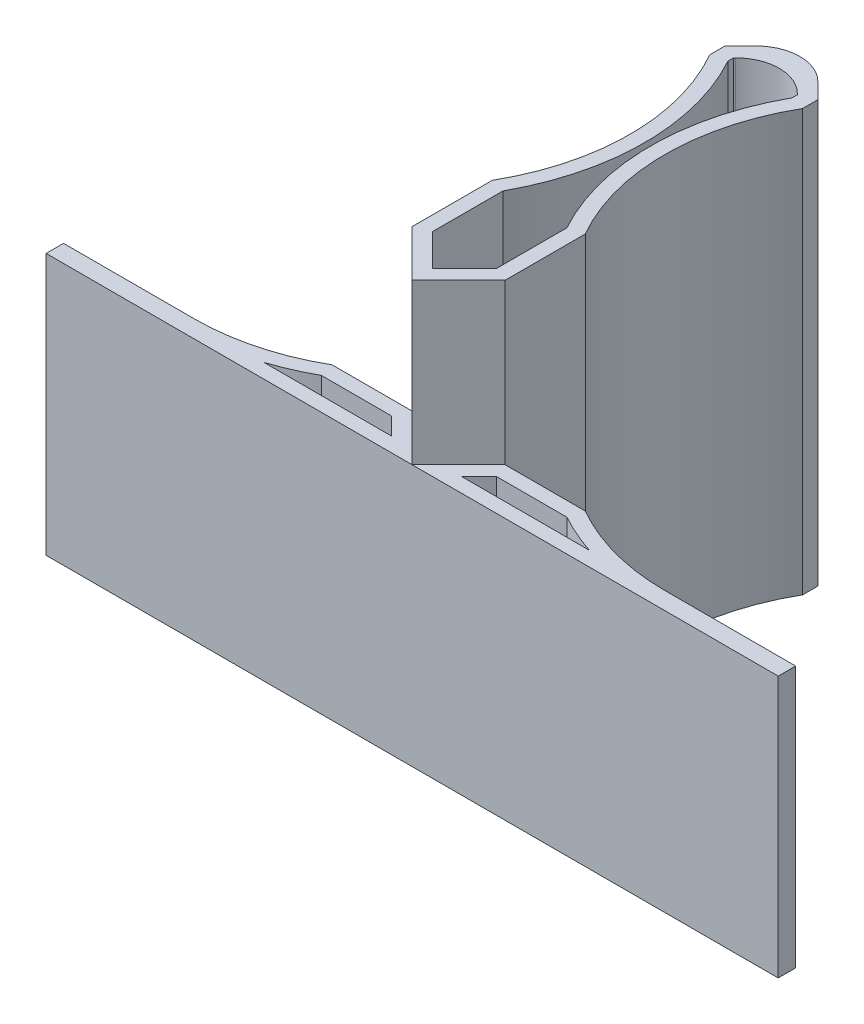
SolidWorks part; units mm, degrees
ref_plane "Front Plane" through (0, 0, 0) normal (0, 0, 1) x (1, 0, 0)
ref_plane "Top Plane" through (0, 0, 0) normal (0, 1, 0) x (1, 0, 0)
ref_plane "Right Plane" through (0, 0, 0) normal (1, 0, 0) x (0, 0, -1)
sketch "Sketch1" plane through (0, 0, 0) normal (0, 1, 0) x (1, 0, 0)
  line L0 (23.7595, 41.275) -> (41.275, 41.275) construction
  line L1 (-41.275, -41.275) -> (-23.7595, -41.275) construction
  line L2 (-41.275, -41.275) -> (-41.275, -23.7595) construction
  line L3 (-41.275, 41.275) -> (-23.7595, 41.275) construction
  line L4 (41.275, -41.275) -> (41.275, -23.7595) construction
  line L5 (-41.275, -41.275) -> (41.275, 41.275) construction
  line L6 (-41.275, 41.275) -> (41.275, -41.275) construction
  line L7 (41.275, 23.7595) -> (41.275, 41.275) construction
  line L8 (-41.275, 23.7595) -> (-41.275, 41.275) construction
  line L9 (23.7595, -41.275) -> (41.275, -41.275) construction
  line L10 (24.7569, 45.085) -> (45.085, 45.085) construction
  line L11 (45.085, 24.7569) -> (45.085, 45.085) construction
  line L12 (45.085, -45.085) -> (45.085, -24.7569) construction
  line L13 (24.7569, -45.085) -> (45.085, -45.085) construction
  line L14 (-45.085, -45.085) -> (-24.7569, -45.085) construction
  line L15 (-45.085, -45.085) -> (-45.085, -24.7569) construction
  line L16 (-45.085, 24.7569) -> (-45.085, 45.085) construction
  line L17 (-45.085, 45.085) -> (-24.7569, 45.085) construction
  line L19 (-51.435, -51.435) -> (51.435, -51.435) construction
  line L20 (-51.435, -51.435) -> (-51.435, 51.435) construction
  line L21 (-51.435, 51.435) -> (51.435, 51.435) construction
  line L22 (51.435, -51.435) -> (51.435, 51.435) construction
  line L23 (-51.435, -51.435) -> (51.435, 51.435) construction
  line L24 (-51.435, 51.435) -> (51.435, -51.435) construction
  arc A1 (-41.275, 23.7595) -> (-41.275, -23.7595) centre (0, 0) ccw construction
  arc A2 (23.7595, 41.275) -> (-23.7595, 41.275) centre (0, 0) ccw construction
  arc A3 (-23.7595, -41.275) -> (23.7595, -41.275) centre (0, 0) ccw construction
  arc A4 (41.275, -23.7595) -> (41.275, 23.7595) centre (0, 0) ccw construction
  arc A5 (45.085, -24.7569) -> (45.085, 24.7569) centre (0, 0) ccw construction
  arc A6 (-24.7569, -45.085) -> (24.7569, -45.085) centre (0, 0) ccw construction
  arc A7 (-45.085, 24.7569) -> (-45.085, -24.7569) centre (0, 0) ccw construction
  arc A8 (24.7569, 45.085) -> (-24.7569, 45.085) centre (0, 0) ccw construction
  point P0 (0, 0)
  dimension "D1" = 82.55
  dimension "D2" = 82.55
  dimension "D3" = 95.25
  dimension "D4" = 3.81
sketch "Sketch2" plane through (0, 0, 0) normal (0, 0, 1) x (1, 0, 0)
  line L0 (0, 48) -> (0, 0) construction
  line L1 (0, 0) -> (0, -9.15) construction
  line L2 (0, 48) -> (0, 82.925) construction
  dimension "Cage height" = 48
  dimension "Plate height" = 34.925
  dimension "D1" = 57.15
  dimension "D2" = 9.15
sketch "Sketch13" plane through (0, 0, 0) normal (0, 1, 0) x (1, 0, 0)
  line L0 (-51.435, -51.435) -> (51.435, -51.435) construction
  line L1 (-41.275, -41.275) -> (-23.7595, -41.275) construction
  line L2 (-41.275, -41.275) -> (-41.275, -23.7595) construction
  line L4 (-51.435, -51.435) -> (0, -51.435)
  line L5 (-41.275, -41.275) -> (-23.7595, -41.275)
  line L6 (-41.275, -41.275) -> (-41.275, -23.7595)
  line L9 (0, -47.625) -> (0, -51.435)
  line L10 (-51.435, 51.435) -> (51.435, -51.435) construction
  line L11 (-41.275, 23.7595) -> (-41.275, 41.275) construction
  line L12 (-51.435, -51.435) -> (-51.435, 51.435) construction
  line L13 (-51.435, 51.435) -> (-41.275, 41.275)
  line L14 (-41.275, 23.7595) -> (-41.275, 41.275)
  line L15 (-51.435, -51.435) -> (-51.435, 51.435)
  arc A0 (-23.7595, -41.275) -> (23.7595, -41.275) centre (0, 0) ccw construction
  arc A2 (-23.7595, -41.275) -> (0, -47.625) centre (0, 0) ccw
  arc A4 (-41.275, 23.7595) -> (-41.275, -23.7595) centre (0, 0) ccw construction
  arc A5 (-41.275, 23.7595) -> (-41.275, -23.7595) centre (0, 0) ccw
extrude "Boss-Extrude2" add sketch "Sketch13" along normal up to vertex (82.925 mm away) and the other way up to vertex (9.15 mm away) up to point (0, 82.925, 0) other way up to point (0, -9.15, 0)
sketch "Sketch15" plane through (0, 82.925, 0) normal (0, 1, 0) x (1, 0, 0)
  line L0 (0, 0) -> (-51.435, -51.435)
  line L1 (-51.435, -51.435) -> (0, -51.435)
  line L2 (0, -51.435) -> (0, 0)
  line L3 (-51.435, -51.435) -> (51.435, -51.435) construction
extrude "Cut-Extrude2" cut sketch "Sketch15" against normal up to vertex (34.925 mm away) up to point (0, 48, 0)
mirror "Mirror1" about plane through (-51.435, 82.925, 51.435) normal (1, 0, 0) of "Boss-Extrude2", "Cut-Extrude2"
sketch "Sketch16" plane through (0, -9.15, 0) normal (0, -1, 0) x (1, 0, 0)
  line L1 (-51.435, -51.435) -> (51.435, -51.435) construction
  circle A5 centre (-51.435, -13.335) radius 1.35
  dimension "D1" = 2.7
  dimension "D2" = 38.1
extrude "Cut-Extrude3" cut sketch "Sketch16" against normal blind 31.75
sketch "Sketch17" plane through (0, 82.925, 0) normal (0, 1, 0) x (1, 0, 0)
  line L0 (7.0944, 7.0944) -> (-7.0944, -7.0944)
  line L1 (7.0944, 7.0944) -> (-44.3406, 58.5294)
  line L2 (-7.0944, -7.0944) -> (-51.435, 37.2462)
  line L3 (-44.3406, 58.5294) -> (-51.435, 51.435)
  line L4 (-41.275, -41.275) -> (41.275, 41.275) construction
  line L5 (-61.595, 41.275) -> (-51.435, 51.435) construction
  line L6 (-51.435, -51.435) -> (-51.435, 51.435) construction
  line L7 (-51.435, 7.7321) -> (-51.435, 82.5591) construction
  line L8 (-95.7756, -7.0944) -> (-51.435, 37.2462)
  line L9 (-58.5294, 58.5294) -> (-51.435, 51.435)
  line L10 (-109.9644, 7.0944) -> (-58.5294, 58.5294)
  line L11 (-109.9644, 7.0944) -> (-95.7756, -7.0944)
  dimension "D1" = 20.066
extrude "Cut-Extrude4" cut sketch "Sketch17" against normal through all
sketch "Sketch18" plane through (0, 82.925, 0) normal (0, 1, 0) x (1, 0, 0)
  line L19 (-58.42, -24.5934) -> (-58.42, -39.9599)
  line L20 (-58.42, -39.9599) -> (-51.435, -46.9449)
  line L21 (-51.435, -46.9449) -> (-44.45, -39.9599)
  line L22 (-44.45, -39.9599) -> (-44.45, -24.5934)
  line L27 (-58.42, -24.5934) -> (-58.42, -39.9599)
  line L28 (-58.42, -39.9599) -> (-51.435, -46.9449)
  line L29 (-51.435, -46.9449) -> (-44.45, -39.9599)
  line L30 (-44.45, -39.9599) -> (-44.45, -24.5934)
  line L32 (-62.9101, -44.45) -> (-78.2766, -44.45)
  line L33 (-87.0077, -48.26) -> (-59.1001, -48.26)
  line L34 (-59.1001, -48.26) -> (-62.9101, -44.45)
  line L35 (-62.9101, -44.45) -> (-78.2766, -44.45)
  line L36 (-87.0077, -48.26) -> (-59.1001, -48.26)
  line L37 (-59.1001, -48.26) -> (-62.9101, -44.45)
  line L42 (-24.5934, -44.45) -> (-39.9599, -44.45)
  line L43 (-39.9599, -44.45) -> (-43.7699, -48.26)
  line L44 (-43.7699, -48.26) -> (-15.8623, -48.26)
  line L45 (-24.5934, -44.45) -> (-39.9599, -44.45)
  line L46 (-39.9599, -44.45) -> (-43.7699, -48.26)
  line L47 (-43.7699, -48.26) -> (-15.8623, -48.26)
  line L48 (-44.45, 25.7711) -> (-51.435, 32.7561)
  line L49 (-44.45, 25.7711) -> (-51.435, 32.7561)
  line L50 (-51.435, 32.7561) -> (-58.42, 25.7711)
  line L51 (-51.435, 32.7561) -> (-58.42, 25.7711)
  line L52 (-58.42, 25.7711) -> (-58.42, 24.5934)
  line L53 (-58.42, 25.7711) -> (-58.42, 24.5934)
  line L54 (-44.45, 24.5934) -> (-44.45, 25.7711)
  line L55 (-44.45, 24.5934) -> (-44.45, 25.7711)
  arc A5 (-87.0077, -48.26) -> (-78.2766, -44.45) centre (-102.87, 0) ccw
  arc A7 (-58.42, -24.5934) -> (-58.42, 24.5934) centre (-102.87, 0) ccw
  arc A8 (-44.45, 24.5934) -> (-44.45, -24.5934) centre (0, 0) ccw
  arc A10 (-58.42, -24.5934) -> (-58.42, 24.5934) centre (-102.87, 0) ccw
  arc A11 (-44.45, 24.5934) -> (-44.45, -24.5934) centre (0, 0) ccw
  arc A12 (-87.0077, -48.26) -> (-78.2766, -44.45) centre (-102.87, 0) ccw
  arc A14 (-24.5934, -44.45) -> (-15.8623, -48.26) centre (0, 0) ccw
  arc A15 (-24.5934, -44.45) -> (-15.8623, -48.26) centre (0, 0) ccw
  dimension "D1" = 3.175
  dimension "D2" = 3.175
  dimension "D3" = 3.175
extrude "Cut-Extrude5" cut sketch "Sketch18" against normal up to surface (60.325 mm away) contours A11 L55 L49 L51 L53 A10 L27 L28 L29 L30 region at (-51.435, 82.925, 12.1349) up to face at (-51.435, 22.6, -14.685)
sketch "Sketch22" plane through (0, 0, 0) normal (0, 1, 0) x (1, 0, 0)
  line L0 (-51.435, -51.435) -> (-51.435, 51.435) construction
  line L1 (-51.435, 51.435) -> (51.435, 51.435) construction
  circle A0 centre (-51.435, -12.065) radius 1.85
  dimension "D1" = 3.7
  dimension "D2" = 63.5
extrude "Cut-Extrude7" cut sketch "Sketch22" against normal through all both and the other way through all
sketch "Sketch20" plane through (0, 22.6, 0) normal (0, 1, 0) x (1, 0, 0)
  line L7 (-56.039, 19.685) -> (-46.831, 19.685)
  line L9 (-47.3448, -18.415) -> (-55.5252, -18.415)
  line L24 (-44.45, 24.5934) -> (-44.45, 25.7711)
  line L25 (-44.45, 25.7711) -> (-51.435, 32.7561)
  line L26 (-51.435, 32.7561) -> (-58.42, 25.7711)
  line L27 (-58.42, 25.7711) -> (-58.42, 24.5934)
  line L28 (-58.42, -24.5934) -> (-58.42, -39.9599)
  line L29 (-58.42, -39.9599) -> (-51.435, -46.9449)
  line L30 (-51.435, -46.9449) -> (-44.45, -39.9599)
  line L31 (-44.45, -39.9599) -> (-44.45, -24.5934)
  line L32 (-44.45, 24.5934) -> (-44.45, 25.7711)
  line L33 (-44.45, 25.7711) -> (-51.435, 32.7561)
  line L34 (-51.435, 32.7561) -> (-58.42, 25.7711)
  line L35 (-58.42, 25.7711) -> (-58.42, 24.5934)
  line L36 (-58.42, -24.5934) -> (-58.42, -39.9599)
  line L37 (-58.42, -39.9599) -> (-51.435, -46.9449)
  line L38 (-51.435, -46.9449) -> (-44.45, -39.9599)
  line L39 (-44.45, -39.9599) -> (-44.45, -24.5934)
  arc A0 (-58.42, -24.5934) -> (-58.42, 24.5934) centre (-102.87, 0) ccw construction
  arc A1 (-47.3448, -18.415) -> (-44.45, -24.5934) centre (0, 0) ccw
  arc A5 (-58.42, -24.5934) -> (-58.42, 24.5934) centre (-102.87, 0) ccw construction
  arc A9 (-44.45, 24.5934) -> (-44.45, -24.5934) centre (0, 0) ccw construction
  arc A11 (-44.45, 24.5934) -> (-44.45, -24.5934) centre (0, 0) ccw construction
  arc A13 (-58.42, -24.5934) -> (-58.42, 24.5934) centre (-102.87, 0) ccw
  arc A14 (-44.45, 24.5934) -> (-44.45, -24.5934) centre (0, 0) ccw
  arc A15 (-58.42, -24.5934) -> (-55.5252, -18.415) centre (-102.87, 0) ccw
  arc A16 (-44.45, 24.5934) -> (-46.831, 19.685) centre (0, 0) ccw
  arc A18 (-56.039, 19.685) -> (-58.42, 24.5934) centre (-102.87, 0) ccw
  circle A19 centre (-51.435, 13.335) radius 1.35 construction
  circle A20 centre (-51.435, -12.065) radius 1.85 construction
  dimension "D2" = 6.35
  dimension "D5" = 6.35
  dimension "D1" = 0
extrude "Cut-Extrude9" cut sketch "Sketch18<3>" against normal through all contours L36 L37 L35 A12 | L45 L46 L47 A15
sketch "Sketch18<3>" plane through (0, 82.925, 0) normal (0, 1, 0) x (1, 0, 0) same geometry as "Sketch18"
extrude "Cut-Extrude10" cut sketch "Sketch20" against normal through all
fillet "Fillet2" radius 9.525 2 edges at (-51.435, 36.8875, -37.2462) (-51.435, 36.8875, -32.7561)
sketch "Sketch23" plane through (0, 48, 0) normal (0, 1, 0) x (1, 0, 0)
  line L1 (0, -51.435) -> (28.575, -51.435)
  line L2 (0, -51.435) -> (0, -47.625)
  line L3 (0, -47.625) -> (28.575, -47.625)
  line L4 (28.575, -51.435) -> (28.575, -47.625)
  line L6 (-102.87, -51.435) -> (-131.445, -51.435)
  line L7 (-102.87, -51.435) -> (-102.87, -47.625)
  line L8 (-102.87, -47.625) -> (-131.445, -47.625)
  line L9 (-131.445, -51.435) -> (-131.445, -47.625)
  point P15 (0, 0)
  dimension "D1" = 28.575
extrude "Boss-Extrude3" add sketch "Sketch23" against normal up to surface (57.15 mm away) up to face at (-51.435, -9.15, -24.3743)
equation "\"tightTol\" = 0.005in"
equation "\"normTol\" = 0.01in"
equation "\"looseTol\" = 0.02in"
equation "\"Cage height@Sketch2\"=48mm"
equation "\"Plate height@Sketch2\"=1.375"
equation "\"D1@Sketch17\"=0.75in+2*\"looseTol\""
equation "\"D1@Sketch22\"=3.7mm"
equation "\"D1@Sketch16\"=2.7mm"
